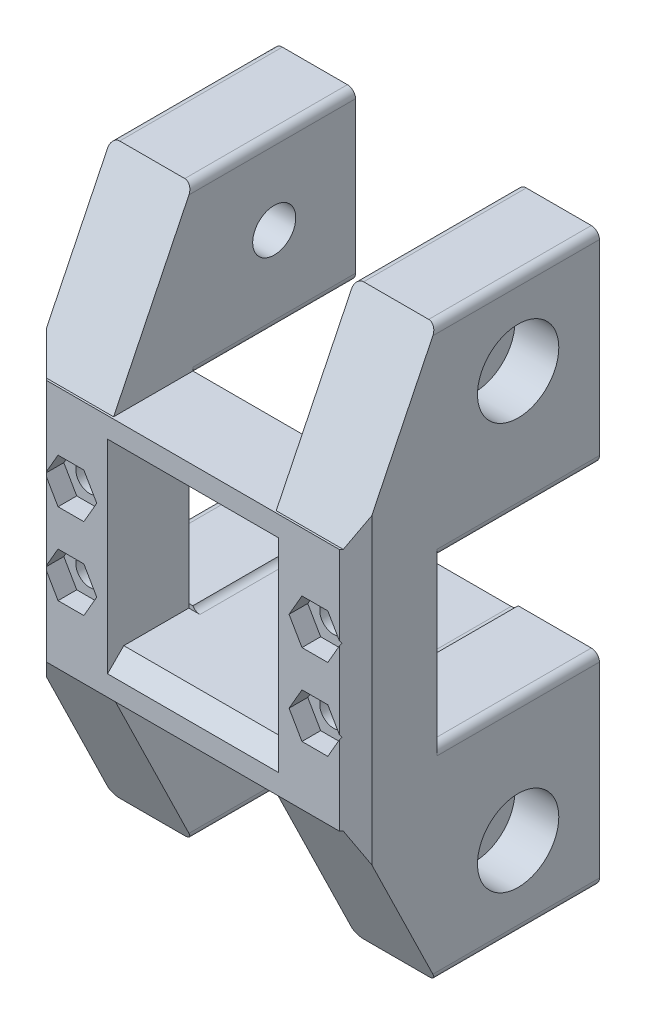
SolidWorks part; units mm, degrees
ref_plane "Front Plane" through (0, 0, 0) normal (0, 0, 1) x (1, 0, 0)
ref_plane "Top Plane" through (0, 0, 0) normal (0, 1, 0) x (1, 0, 0)
ref_plane "Right Plane" through (0, 0, 0) normal (1, 0, 0) x (0, 0, -1)
ref_plane "Mount Thickness" through (0, 0, 10) normal (0, 0, 1) x (1, 0, 0)
sketch "Main Body Sketch" plane through (0, 0, 0) normal (0, 0, 1) x (1, 0, 0)
  line L0 (-10, 30) -> (30, 30) construction
  line L1 (-10, 30) -> (30, 30)
  line L2 (30, 30) -> (30, 25) construction
  line L3 (30, 15) -> (30, 25) construction
  line L4 (30, 15) -> (30, 0) construction
  line L5 (-10, 0) -> (30, 0) construction
  line L6 (-10, 15) -> (-10, 0) construction
  line L7 (-10, 15) -> (-10, 25) construction
  line L8 (-10, 30) -> (-10, 25) construction
  line L9 (30, 30) -> (30, 25)
  line L10 (30, 15) -> (30, 25)
  line L11 (30, 15) -> (30, 0)
  line L12 (-10, 0) -> (30, 0)
  line L13 (-10, 15) -> (-10, 0)
  line L14 (-10, 15) -> (-10, 25)
  line L15 (-10, 30) -> (-10, 25)
  line L16 (10, 0) -> (10, 80.4727) construction
  line L17 (10, 0) -> (10, 80.4727) construction
  line L18 (0, 15) -> (20, 15) construction
  line L20 (-0.5, 4.5) -> (20.5, 4.5)
  line L21 (-0.5, 4.5) -> (-0.5, 25.5)
  line L22 (-0.5, 25.5) -> (20.5, 25.5)
  line L23 (20.5, 4.5) -> (20.5, 25.5)
  line L24 (-0.5, 4.5) -> (20.5, 25.5) construction
  line L25 (-0.5, 25.5) -> (20.5, 4.5) construction
  point P11 (10, 15)
  point P14 (10, 15)
  dimension "D1" = 0.5
extrude "Main Mounting Face" add sketch "Main Body Sketch" along normal up to surface (10 mm away) up to plane "Mount Thickness"
ref_plane "Extrusion Mounting Bottom Plane" through (0, 4.5, 0) normal (0, 1, 0) x (1, 0, 0)
ref_plane "Top Extrusion Mounting Bottom Plane" through (0, 25.5, 0) normal (0, 1, 0) x (1, 0, 0)
ref_plane "Top Extrusion Mounting Top Plane" through (0, 30, 0) normal (0, 1, 0) x (1, 0, 0)
sketch "Extrusion Bottom Mounting Sketch" plane through (0, 0, 0) normal (0, 1, 0) x (1, 0, 0)
  line L1 (0, 0) -> (20, 0)
  line L2 (0, 0) -> (0, 20)
  line L3 (0, 20) -> (20, 20)
  line L4 (20, 0) -> (20, 20)
  dimension "D1" = 20
extrude "Bottom Extrusion Mounting Block" add sketch "Extrusion Bottom Mounting Sketch" along normal up to surface (4.5 mm away) up to plane "Extrusion Mounting Bottom Plane"
hole_wizard "Tension Bolt Holes (M3)" positions "Sketch3" profile "Sketch4" hole size "M3" standard "ISO" end condition through all
sketch "Sketch3" plane through (0, 0, 10) normal (0, 0, 1) x (1, 0, 0)
  point P0 (-5, 20)
  point P3 (-5, 10)
  point P6 (25, 10)
  point P9 (25, 20)
sketch "Sketch4" plane through (-5, 20, 10) normal (1, 0, 0) x (0, -1, 0)
  line L0 (0, 0) -> (0, 30)
  line L1 (0, 30) -> (1.7, 30)
  line L2 (1.7, 30) -> (1.7, 0)
  line L5 (1.7, 0) -> (0, 0)
  line L11 (0, -6.35) -> (0, 107.95) construction
  dimension "Thru Hole Dia." = 3.4
  dimension "Thru Hole Depth" = 30
sketch "Nut Trap Sketch" plane through (0, 0, 10) normal (0, 0, 1) x (1, 0, 0)
  line L0 (0, 15) -> (20, 15) construction
  line L1 (-3.4123, 22.75) -> (-6.5877, 22.75)
  line L2 (-6.5877, 22.75) -> (-8.1754, 20)
  line L3 (-8.1754, 20) -> (-6.5877, 17.25)
  line L4 (-6.5877, 17.25) -> (-3.4123, 17.25)
  line L5 (-3.4123, 17.25) -> (-1.8246, 20)
  line L6 (-1.8246, 20) -> (-3.4123, 22.75)
  line L7 (10, 0) -> (10, 80.4727) construction
  line L8 (0, 15) -> (20, 15) construction
  line L9 (10, 0) -> (10, 80.4727) construction
  line L10 (-1.8246, 10) -> (-3.4123, 7.25)
  line L11 (-3.4123, 12.75) -> (-1.8246, 10)
  line L12 (-6.5877, 12.75) -> (-3.4123, 12.75)
  line L13 (-8.1754, 10) -> (-6.5877, 12.75)
  line L14 (-6.5877, 7.25) -> (-8.1754, 10)
  line L15 (-3.4123, 7.25) -> (-6.5877, 7.25)
  line L16 (23.4123, 7.25) -> (26.5877, 7.25)
  line L17 (26.5877, 7.25) -> (28.1754, 10)
  line L18 (28.1754, 10) -> (26.5877, 12.75)
  line L19 (26.5877, 12.75) -> (23.4123, 12.75)
  line L20 (23.4123, 12.75) -> (21.8246, 10)
  line L21 (21.8246, 10) -> (23.4123, 7.25)
  line L22 (21.8246, 20) -> (23.4123, 22.75)
  line L23 (23.4123, 17.25) -> (21.8246, 20)
  line L24 (26.5877, 17.25) -> (23.4123, 17.25)
  line L25 (28.1754, 20) -> (26.5877, 17.25)
  line L26 (26.5877, 22.75) -> (28.1754, 20)
  line L27 (23.4123, 22.75) -> (26.5877, 22.75)
  circle A0 centre (-5, 20) radius 2.75 construction
  circle A1 centre (-5, 10) radius 2.75 construction
  circle A2 centre (25, 10) radius 2.75 construction
  circle A3 centre (25, 20) radius 2.75 construction
  dimension "D1" = 5.5
extrude "Nut Traps (M3)" cut sketch "Nut Trap Sketch" against normal blind 2.3
sketch "Tension Slot Sketch" plane through (0, 4.5, 0) normal (0, 1, 0) x (1, 0, 0)
  line L0 (12.5, 10) -> (12.5, 5) construction
  line L1 (12.5, 10) -> (12.5, 5)
  line L2 (7.5, 10) -> (7.5, 5) construction
  line L3 (7.5, 10) -> (7.5, 5)
  arc A0 (7.5, 5) -> (12.5, 5) centre (10, 5) ccw construction
  arc A1 (12.5, 10) -> (7.5, 10) centre (10, 10) ccw construction
  arc A2 (7.5, 5) -> (12.5, 5) centre (10, 5) ccw
  arc A3 (12.5, 10) -> (7.5, 10) centre (10, 10) ccw
extrude "Tension Slot - Bottom" cut sketch "Tension Slot Sketch" against normal through all
sketch "Extrusion Mounting Holes Position Sketch" plane through (0, 0, 0) normal (1, 0, 0) x (0, 0, -1)
  line L0 (0, 30) -> (0, 50) construction
  line L1 (0, 30) -> (0, 50) construction
  line L2 (0, 30) -> (20, 30) construction
  line L3 (20, 30) -> (20, 50) construction
  line L4 (20, 50) -> (0, 50) construction
  line L6 (0, 0) -> (20, 0) construction
  line L7 (0, 0) -> (20, 0) construction
  line L8 (20, 30) -> (0, 50) construction
  line L9 (0, 15) -> (12.5625, 15) construction
  point P7 (10, -10)
  point P8 (10, 40)
  point P9 (0, 15)
sketch "Main Extrusion Mounts Sketch" plane through (0, 0, 0) normal (0, 0, 1) x (1, 0, 0)
  line L0 (0, 15) -> (20, 15) construction
  line L1 (0, 15) -> (20, 15) construction
  line L10 (30, 5) -> (30, -20)
  line L11 (0, 25) -> (-10, 25)
  line L12 (0, 25) -> (0, 50)
  line L13 (0, 50) -> (-10, 50)
  line L14 (-10, 25) -> (-10, 50)
  line L15 (20, 25) -> (30, 25)
  line L16 (20, 25) -> (20, 50)
  line L17 (20, 50) -> (30, 50)
  line L18 (30, 25) -> (30, 50)
  line L19 (20, -20) -> (30, -20)
  line L20 (20, 5) -> (20, -20)
  line L21 (20, 5) -> (30, 5)
  line L22 (-10, 5) -> (-10, -20)
  line L23 (0, -20) -> (-10, -20)
  line L24 (0, 5) -> (0, -20)
  line L25 (0, 5) -> (-10, 5)
  line L26 (-0.5, 25.5) -> (20.5, 4.5) construction
  line L27 (-0.5, 4.5) -> (20.5, 25.5) construction
  line L28 (20, 25) -> (20, 15) construction
extrude "Main Extrusion Mounts" add sketch "Main Extrusion Mounts Sketch" against normal up to vertex (20 mm away) up to point (0, 50, -20)
hole_wizard "Extrusion Mounting Bolt Holes (R)" positions "Sketch16" profile "Sketch17" counterbore size "M5" standard "ISO" end condition through all
sketch "Sketch16" plane through (-10, 0, 0) normal (-1, 0, 0) x (0, 0, 1)
  point P0 (-10, 40)
  point P3 (-10, -10)
sketch "Sketch17" plane through (-10, 40, -10) normal (0, 1, 0) x (0, 0, 1)
  line L0 (0, 0) -> (0, 40)
  line L1 (0, 40) -> (2.65, 40)
  line L3 (2.65, 40) -> (2.65, 5.4)
  line L4 (2.65, 5.4) -> (5, 5.4)
  line L5 (5, 5.4) -> (5, 0)
  line L7 (5, 0) -> (0, 0)
  line L11 (0, -6.35) -> (0, 107.95) construction
  dimension "Thru Hole Dia." = 5.3
  dimension "Thru Hole Depth" = 40
  dimension "C'Bore Dia." = 10
  dimension "C'Bore Depth" = 5.4
hole_wizard "Extrusion Mounting Bolt Holes (L)" positions "Sketch18" profile "Sketch19" counterbore size "M5" standard "ISO" end condition through all
sketch "Sketch18" plane through (30, 0, 0) normal (1, 0, 0) x (0, 0, -1)
  point P0 (10, 40)
  point P3 (10, -10)
sketch "Sketch19" plane through (30, 40, -10) normal (0, 1, 0) x (0, 0, -1)
  line L0 (0, 0) -> (0, 40)
  line L1 (0, 40) -> (2.65, 40)
  line L3 (2.65, 40) -> (2.65, 5.4)
  line L4 (2.65, 5.4) -> (5, 5.4)
  line L5 (5, 5.4) -> (5, 0)
  line L7 (5, 0) -> (0, 0)
  line L11 (0, -6.35) -> (0, 107.95) construction
  dimension "Thru Hole Dia." = 5.3
  dimension "Thru Hole Depth" = 40
  dimension "C'Bore Dia." = 10
  dimension "C'Bore Depth" = 5.4
chamfer "Clearance Chamfers" distance 5 angle 45 2 edges at (0, 25, -10) (20, 25, -10)
chamfer "Stengthening Chamfers" distance 20 angle 26 4 edges at (25, 30, 0) (-5, 30, 0) (25, 0, 0) (-5, 0, 0) first distance on face at (25, 40, 0) first distance on face at (-5, 40, 0) first distance on face at (25, -10, 0) first distance on face at (-5, -10, 0)
chamfer "Cosmetic Chamfers" distance 2 angle 45 4 edges at (30, 15, 10) (-10, 15, 10) (10, 25.5, 10) (10, 4.5, 10)
fillet "Print Helper Fillets" radius 1 18 edges at (0, 4.5, -10) (20, 4.5, -10) (0, 30, -10) (-5, 25, -10) (25, 25, -10) (20, 30, -10) (-10, 25, -10) (-10, 5, -10) (30, 5, -10) (30, 25, -10) (30, -20, -10) (20, -20, -10) (0, -20, -10) (-10, -20, -10) (-10, 50, -10) (0, 50, -10) (20, 50, -10) (30, 50, -10)
